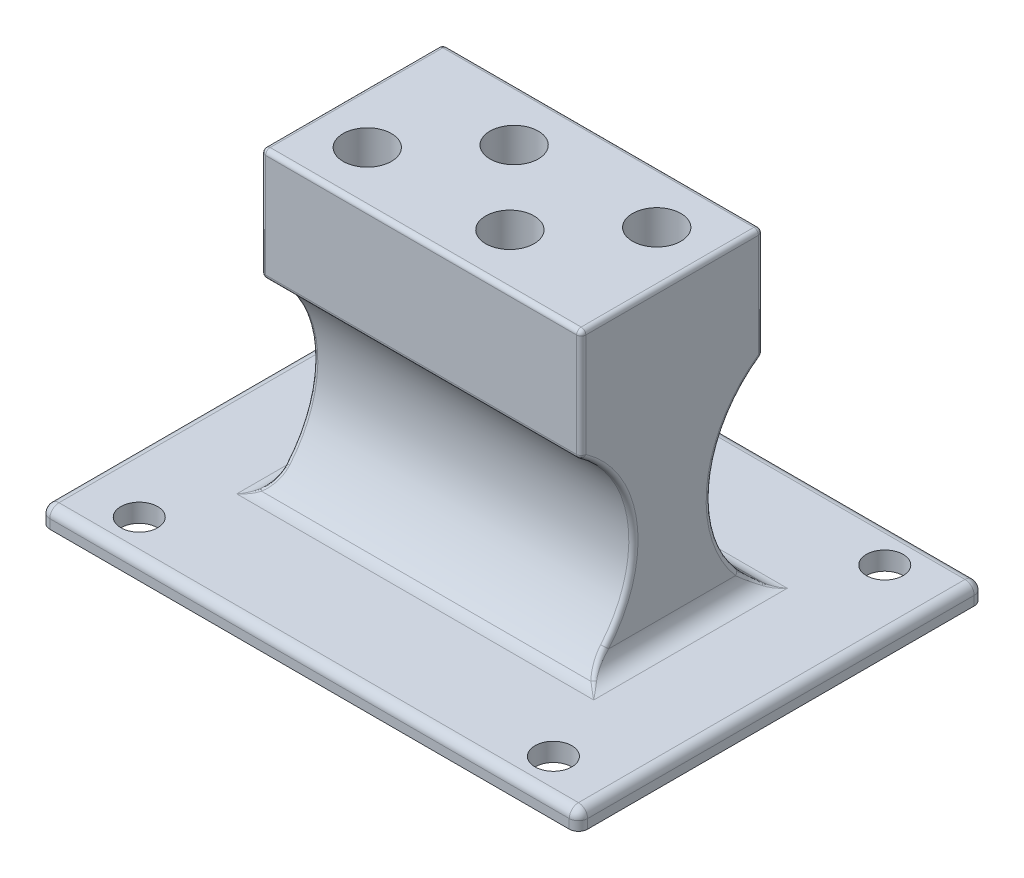
SolidWorks part; units mm, degrees
material "Acrylic (Medium-high impact)"
ref_plane "Front Plane" through (0, 0, 0) normal (0, 0, 1) x (1, 0, 0)
ref_plane "Top Plane" through (0, 0, 0) normal (0, 1, 0) x (1, 0, 0)
ref_plane "Right Plane" through (0, 0, 0) normal (1, 0, 0) x (0, 0, -1)
sketch "Sketch3" plane through (0, 0, 0) normal (0, 1, 0) x (1, 0, 0)
  line L1 (-92.7735, -69.85) -> (92.7735, -69.85)
  line L2 (-92.7735, -69.85) -> (-92.7735, 69.85)
  line L3 (-92.7735, 69.85) -> (92.7735, 69.85)
  line L4 (92.7735, -69.85) -> (92.7735, 69.85)
  line L5 (-92.7735, -69.85) -> (92.7735, 69.85) construction
  line L6 (-92.7735, 69.85) -> (92.7735, -69.85) construction
  point P0 (0, 0)
  dimension "D1" = 185.547
  dimension "D2" = 139.7
extrude "Boss-Extrude1" add sketch "Sketch3" along normal blind 6.35
sketch "Sketch4" plane through (0, 0, 0) normal (0, -1, 0) x (-1, 0, 0)
  line L0 (92.7735, 0) -> (36.8935, 0) construction
  line L1 (92.7735, 69.85) -> (92.7735, -69.85) construction
  line L2 (36.8935, 0) -> (12.2978, 0) construction
  line L3 (12.2978, 0) -> (-12.2978, 0) construction
  line L4 (-12.2978, 0) -> (-36.8935, 0) construction
  line L5 (-36.8935, 0) -> (-92.7735, 0) construction
  line L6 (-92.7735, -69.85) -> (-92.7735, 69.85) construction
  circle A0 centre (36.8935, 0) radius 8.3344
  circle A1 centre (12.2978, 0) radius 8.3344
  circle A2 centre (-12.2978, 0) radius 8.3344
  circle A3 centre (-36.8935, 0) radius 8.3344
  dimension "D1" = 16.6687
  dimension "D2" = 55.88
  dimension "D3" = 55.88
sketch "Sketch9" plane through (0, 6.35, 0) normal (0, 1, 0) x (1, 0, 0)
  line L0 (36.8935, 8.3344) -> (36.8935, 31.3653) construction
  line L1 (-55.2279, -31.3653) -> (55.2279, -31.3653)
  line L2 (-55.2279, -31.3653) -> (-55.2279, 31.3653)
  line L3 (-55.2279, 31.3653) -> (55.2279, 31.3653)
  line L4 (55.2279, -31.3653) -> (55.2279, 31.3653)
  line L5 (-55.2279, -31.3653) -> (55.2279, 31.3653) construction
  line L6 (-55.2279, 31.3653) -> (55.2279, -31.3653) construction
  line L7 (45.2279, 0) -> (55.2279, 0) construction
  circle A0 centre (36.8935, 0) radius 8.3344 construction
  point P0 (0, 0)
  dimension "D1" = 62.7307
  dimension "D2" = 110.4558
extrude "Boss-Extrude4" add sketch "Sketch9" along normal blind 105.6523
ref_plane "Plane1" through (-36.8935, 0, 0) normal (-1, 0, 0) x (0, 0, 1)
ref_plane "Plane2" through (-12.2978, 0, 0) normal (-1, 0, 0) x (0, 0, 1)
sketch "Sketch5" plane through (-36.8935, 0, 0) normal (-1, 0, 0) x (0, 0, 1)
  line L0 (0, 0) -> (0, 48.5606)
  line L1 (0.7659, 52.9043) -> (12.2651, 84.498)
  line L2 (13.031, 88.8416) -> (13.031, 162.1245)
  arc A0 (12.2651, 84.498) -> (13.031, 88.8416) centre (0.331, 88.8416) ccw
  arc A1 (0, 48.5606) -> (0.7659, 52.9043) centre (12.7, 48.5606) cw
  point P7 (13.031, 86.6023)
  point P10 (0, 50.8)
  dimension "D4" = 12.7
  dimension "D1" = 50.8
  dimension "D2" = 38.1
  dimension "D3" = 160
sweep "Cut-Sweep1" cut profiles "Sketch4" path "Sketch5"
sketch "Sketch6" plane through (-12.2978, 0, 0) normal (-1, 0, 0) x (0, 0, 1)
  line L0 (0, 0) -> (0, 48.5606)
  line L1 (-0.7659, 52.9043) -> (-12.2651, 84.498)
  line L2 (-13.031, 88.8416) -> (-13.031, 164.3029)
  arc A0 (-12.2651, 84.498) -> (-13.031, 88.8416) centre (-0.331, 88.8416) cw
  arc A1 (0, 48.5606) -> (-0.7659, 52.9043) centre (-12.7, 48.5606) ccw
  point P7 (-13.031, 86.6023)
  point P10 (0, 50.8)
  dimension "D3" = 12.7
  dimension "D1" = 50.8
  dimension "D2" = 38.1
  dimension "D4" = 160
sweep "Cut-Sweep2" cut profiles "Sketch4<3>" path "Sketch6"
sketch "Sketch4<3>" plane through (0, 0, 0) normal (0, -1, 0) x (-1, 0, 0) same geometry as "Sketch4"
sweep "Cut-Sweep3" cut profiles "Sketch4<4>" path "Sketch5<2>"
sketch "Sketch4<4>" plane through (0, 0, 0) normal (0, -1, 0) x (-1, 0, 0) same geometry as "Sketch4"
sketch "Sketch5<2>" plane through (-36.8935, 0, 0) normal (-1, 0, 0) x (0, 0, 1) same geometry as "Sketch5"
sweep "Cut-Sweep4" cut profiles "Sketch4<5>" path "Sketch6<2>"
sketch "Sketch4<5>" plane through (0, 0, 0) normal (0, -1, 0) x (-1, 0, 0) same geometry as "Sketch4"
sketch "Sketch6<2>" plane through (-12.2978, 0, 0) normal (-1, 0, 0) x (0, 0, 1) same geometry as "Sketch6"
sketch "Sketch7" plane through (0, 6.35, 0) normal (0, 1, 0) x (1, 0, 0)
  line L0 (-71.4375, 57.15) -> (71.4375, 57.15) construction
  line L1 (71.4375, 57.15) -> (71.4375, -57.15) construction
  line L2 (71.4375, -57.15) -> (-71.4375, -57.15) construction
  line L3 (-71.4375, -57.15) -> (-71.4375, 57.15) construction
  line L4 (92.7735, 69.85) -> (-92.7735, 69.85) construction
  line L5 (-92.7735, -69.85) -> (92.7735, -69.85) construction
  line L6 (-92.7735, 69.85) -> (-92.7735, -69.85) construction
  line L7 (92.7735, -69.85) -> (92.7735, 69.85) construction
  circle A0 centre (-71.4375, 57.15) radius 6.35
  circle A1 centre (71.4375, 57.15) radius 6.35
  circle A2 centre (71.4375, -57.15) radius 6.35
  circle A3 centre (-71.4375, -57.15) radius 6.35
  dimension "D1" = 12.7
  dimension "D2" = 12.7
  dimension "D3" = 12.7
  dimension "D4" = 21.336
  dimension "D5" = 21.336
extrude "Cut-Extrude1" cut sketch "Sketch7" against normal through all
fillet "Fillet1" radius 3.175 8 edges at (-92.7735, 3.175, -69.85) (92.7735, 3.175, -69.85) (92.7735, 3.175, 69.85) (-92.7735, 3.175, 69.85) (0, 6.35, 69.85) (92.7735, 6.35, 0) (-92.7735, 6.35, 0) (0, 6.35, -69.85)
ref_plane "Plane3" through (0, 0, -8.3344) normal (0, 0, 1) x (1, 0, 0)
sketch "Sketch10" plane through (55.2279, 0, 0) normal (1, 0, 0) x (0, 0, -1)
  line L1 (31.3653, 6.35) -> (31.3653, 73.9023)
  line L2 (13.3344, 40.1261) -> (8.3344, 40.1261) construction
  line L3 (8.3344, 60.7507) -> (8.3344, -60.7507) construction
  arc A0 (31.3653, 6.35) -> (31.3653, 73.9023) centre (53.9851, 40.1261) cw
  dimension "D1" = 5
  dimension "D2" = 38.1
extrude "Cut-Extrude3" cut sketch "Sketch10" against normal through all
mirror "Mirror2" about plane through (0, 0, 0) normal (0, 0, 1) of "Cut-Extrude3"
fillet "Fillet3" radius 6.35 4 edges at (-55.2279, 6.35, 0) (0, 6.35, 31.3653) (55.2279, 6.35, 0) (0, 6.35, -31.3653)
fillet "Fillet4" radius 1.5875 22 edges at (-59.5677, 6.6766, 31.3753) (-55.8874, 9.882, 26.8232) (59.5677, 6.6766, 31.3753) (56.1684, 9.3743, 27.3993) (-59.5677, 6.6766, -31.3753) (-56.1684, 9.3743, -27.3993) (59.5677, 6.6766, -31.3753) (55.8874, 9.882, -26.8232) (-55.2279, 112.0023, 0) (0, 112.0023, 31.3653) (0, 73.9023, 31.3653) (-55.2279, 92.9523, 31.3653) (-55.2279, 44.996, 13.6271) (-55.2279, 92.9523, -31.3653) (55.2279, 92.9523, 31.3653) (55.2279, 112.0023, 0) (0, 112.0023, -31.3653) (0, 73.9023, -31.3653) (55.2279, 92.9523, -31.3653) (55.2279, 44.996, 13.6271) (-55.2279, 44.996, -13.6271) (55.2279, 44.996, -13.6271)
